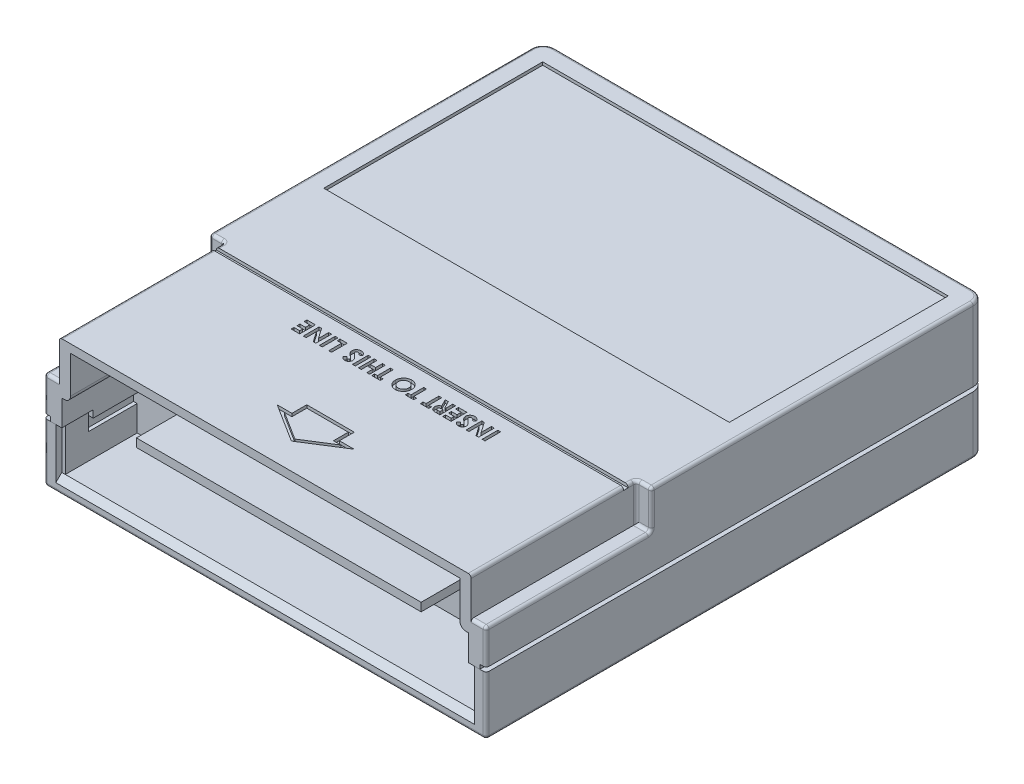
SolidWorks part; units mm, degrees
other "PCB"
other "Back"
other "Front"
ref_plane "Front Plane" through (0, 0, 0) normal (0, 0, 1) x (1, 0, 0)
ref_plane "Top Plane" through (0, 0, 0) normal (0, 1, 0) x (1, 0, 0)
ref_plane "Right Plane" through (0, 0, 0) normal (1, 0, 0) x (0, 0, -1)
sketch "Sketch1" plane through (0, 0, 0) normal (0, 1, 0) x (1, 0, 0)
  line L0 (0, 0) -> (0, 65.8) construction
  line L1 (-23.975, 0) -> (-23.975, 21.47)
  line L2 (-23.975, 21.47) -> (-26.93, 21.47)
  line L3 (-26.93, 21.47) -> (-26.93, 65.8)
  line L4 (-26.93, 65.8) -> (26.93, 65.8)
  line L5 (26.93, 65.8) -> (26.93, 21.47)
  line L6 (26.93, 21.47) -> (23.975, 21.47)
  line L7 (23.975, 21.47) -> (23.975, 0)
  line L8 (23.975, 0) -> (-23.975, 0)
  line L9 (-20.025, 17.13) -> (20.025, 17.13) construction
  circle A0 centre (-20.025, 19.03) radius 1.9
  circle A1 centre (0, 19.03) radius 2.65
  circle A2 centre (20.025, 19.03) radius 1.9
  point P16 (0, 0)
  dimension "D5" = 3.8
  dimension "D8" = 5.3
  dimension "D1" = 53.86
  dimension "D2" = 44.33
  dimension "D3" = 65.8
  dimension "D4" = 47.95
  dimension "D6" = 36.25
  dimension "D7" = 17.13
extrude "Boss-Extrude1" add sketch "Sketch1" along normal mid plane 1.6
sketch "Sketch2" plane through (0, 0.8, 0) normal (0, 1, 0) x (1, 0, 0)
  line L0 (0, 0) -> (0, 65.8) construction
  line L1 (-26.125, 39.52) -> (26.125, 39.52)
  line L2 (-26.125, 39.52) -> (-26.125, 25.82)
  line L3 (-26.125, 25.82) -> (26.125, 25.82)
  line L4 (26.125, 39.52) -> (26.125, 25.82)
  line L5 (26.93, 65.8) -> (-26.93, 65.8) construction
  line L6 (-23.975, 0) -> (23.975, 0) construction
  dimension "D1" = 52.25
  dimension "D2" = 13.7
  dimension "D3" = 25.82
extrude "Boss-Extrude2" add sketch "Sketch2" along normal blind 4.4
sketch "Sketch3" plane through (0, 0.8, 0) normal (0, 1, 0) x (1, 0, 0)
  line L0 (26.93, 21.47) -> (26.93, 65.8) construction
  line L1 (11.66, 63.46) -> (22.66, 63.46)
  line L2 (11.66, 63.46) -> (11.66, 42.86)
  line L3 (11.66, 42.86) -> (22.66, 42.86)
  line L4 (22.66, 63.46) -> (22.66, 42.86)
  line L5 (26.93, 65.8) -> (-26.93, 65.8) construction
  dimension "D1" = 20.6
  dimension "D2" = 11
  dimension "D3" = 4.27
  dimension "D4" = 2.34
extrude "Boss-Extrude3" add sketch "Sketch3" along normal blind 2.88
sketch "Sketch4" plane through (0, 0.8, 0) normal (0, 1, 0) x (1, 0, 0)
  line L0 (26.93, 65.8) -> (-26.93, 65.8) construction
  line L1 (0, 54.1) -> (0, 19.03) construction
  circle A0 centre (0, 54.1) radius 1.6
  dimension "D1" = 3.2
  dimension "D2" = 10.1
extrude "Boss-Extrude4" add sketch "Sketch4" along normal blind 6.75
sketch "Sketch5" plane through (0, 0.8, 0) normal (0, 1, 0) x (1, 0, 0)
  line L0 (23.975, 0) -> (23.975, 21.47) construction
  line L1 (-23.975, 0) -> (23.975, 0)
  line L2 (-23.975, 0) -> (-23.975, 8.52)
  line L3 (-23.975, 8.52) -> (23.975, 8.52)
  line L4 (23.975, 0) -> (23.975, 8.52)
  dimension "D1" = 8.52
extrude "Cut-Extrude1" cut sketch "Sketch5" against normal blind 0.1
mirror "Mirror1" about plane through (0, 0, 0) normal (0, 1, 0) of "Cut-Extrude1"
ref_plane "Plane1" through (0, -4.72, 0) normal (0, -1, 0) x (-1, 0, 0)
sketch "Sketch6" plane through (0, -4.72, 0) normal (0, -1, 0) x (-1, 0, 0)
  line L0 (0, 19.03) -> (0, 38.8) construction
  line L1 (-11.845, 38.8) -> (11.845, 38.8)
  line L2 (-11.845, 38.8) -> (-11.845, 80.73)
  line L3 (-11.845, 80.73) -> (11.845, 80.73)
  line L4 (11.845, 38.8) -> (11.845, 80.73)
  line L5 (23.975, 0) -> (-23.975, 0) construction
  dimension "D1" = 41.93
  dimension "D2" = 23.69
  dimension "D3" = 38.8
extrude "Boss-Extrude5" add sketch "Sketch6" along normal blind 1.09 separate body
sketch "Sketch7" plane through (0, -4.72, 0) normal (0, 1, 0) x (1, 0, 0)
  line L0 (0, 80.73) -> (0, 47.8) construction
  line L1 (-7.5, 47.8) -> (7.5, 47.8)
  line L2 (-7.5, 47.8) -> (-7.5, 43.8)
  line L3 (-7.5, 43.8) -> (7.5, 43.8)
  line L4 (7.5, 47.8) -> (7.5, 43.8)
  line L5 (-11.845, 80.73) -> (11.845, 80.73) construction
  line L6 (11.845, 38.8) -> (-11.845, 38.8) construction
  dimension "D1" = 15
  dimension "D2" = 4
  dimension "D3" = 5
extrude "Boss-Extrude6" add sketch "Sketch7" along normal up to next
sketch "Sketch8" plane through (0, -4.72, 0) normal (0, 1, 0) x (1, 0, 0)
  line L0 (-5, 80.73) -> (-3.795, 79.37)
  line L1 (-11.845, 80.73) -> (11.845, 80.73) construction
  line L2 (-3.795, 79.37) -> (3.795, 79.37)
  line L3 (3.795, 79.37) -> (5, 80.73)
  line L4 (5, 80.73) -> (-5, 80.73)
  line L5 (0, 79.37) -> (0, 65.8) construction
  line L6 (26.93, 65.8) -> (-26.93, 65.8) construction
  dimension "D1" = 7.59
  dimension "D2" = 1.36
  dimension "D3" = 10
extrude "Cut-Extrude2" cut sketch "Sketch8" against normal through all both and the other way through all
sketch "Sketch9" plane through (0, -4.72, 0) normal (0, 1, 0) x (1, 0, 0)
  line L0 (0, 79.37) -> (0, 77.88) construction
  line L1 (-7.5, 77.88) -> (7.5, 77.88)
  line L2 (-7.5, 77.88) -> (-7.5, 62.13)
  line L3 (-7.5, 62.13) -> (7.5, 62.13)
  line L4 (7.5, 77.88) -> (7.5, 62.13)
  line L5 (-3.795, 79.37) -> (3.795, 79.37) construction
  line L6 (-11.845, 80.73) -> (-5, 80.73) construction
  dimension "D1" = 15
  dimension "D2" = 2.85
  dimension "D3" = 15.75
extrude "Boss-Extrude7" add sketch "Sketch9" along normal blind 1.95
sketch "Sketch41" plane through (0, 0, -77.88) normal (0, 0, -1) x (-1, 0, 0)
  line L1 (-6.63, -2.87) -> (4.39, -2.87)
  line L2 (-6.63, -2.87) -> (-6.63, -3.87)
  line L3 (-6.63, -3.87) -> (4.39, -3.87)
  line L4 (4.39, -2.87) -> (4.39, -3.87)
  line L5 (-7.5, -2.77) -> (-7.5, -4.72) construction
  line L6 (-7.5, -2.77) -> (7.5, -2.77) construction
  dimension "D1" = 11.02
  dimension "D2" = 0.87
  dimension "D3" = 0.1
  dimension "D4" = 1
extrude "Boss-Extrude25" add sketch "Sketch41" along normal blind 2.42 separate body
sketch "Sketch10" plane through (0, 0.8, 0) normal (0, 1, 0) x (1, 0, 0)
  line L0 (0, 0) -> (0, 87.284) construction
  circle A0 centre (-20.025, 19.03) radius 1.73
  circle A1 centre (0, 19.03) radius 2.47
  circle A2 centre (20.025, 19.03) radius 1.73
  circle A3 centre (0, 19.03) radius 1.515
  circle A4 centre (-27, 73.03) radius 3.28
  circle A5 centre (27, 73.03) radius 3.28
  circle A6 centre (-27, 73.03) radius 1.515
  circle A7 centre (27, 73.03) radius 1.515
  dimension "D1" = 3.46
  dimension "D2" = 4.94
  dimension "D3" = 3.03
  dimension "D4" = 6.56
  dimension "D5" = 54
  dimension "D6" = 54
extrude "Boss-Extrude8" add sketch "Sketch10" against normal up to surface (1.6 mm away) separate body up to face at (0, -0.8, -16.38)
sketch "Sketch11" plane through (0, -0.8, 0) normal (0, -1, 0) x (1, 0, 0)
  circle A0 centre (20.025, -19.03) radius 2.5
  circle A1 centre (-20.025, -19.03) radius 2.5
  circle A2 centre (0, -19.03) radius 1.515
  circle A3 centre (0, -19.03) radius 3.28
  circle A4 centre (0, -19.03) radius 1.515 construction
  circle A5 centre (27, -73.03) radius 3.28 construction
  circle A6 centre (-27, -73.03) radius 3.28 construction
  circle A7 centre (27, -73.03) radius 3.28
  circle A8 centre (-27, -73.03) radius 3.28
  circle A9 centre (-27, -73.03) radius 1.515 construction
  circle A10 centre (27, -73.03) radius 1.515 construction
  circle A11 centre (-27, -73.03) radius 1.515
  circle A12 centre (27, -73.03) radius 1.515
  dimension "D1" = 5
  dimension "D2" = 6.56
extrude "Boss-Extrude9" add sketch "Sketch11" along normal blind 8.535 separate body
sketch "Sketch12" plane through (0, -9.335, 0) normal (0, -1, 0) x (1, 0, 0)
  circle A0 centre (0, -19.03) radius 1.515
  circle A1 centre (0, -19.03) radius 4.625
  circle A2 centre (0, -19.03) radius 1.515 construction
  circle A3 centre (-27, -73.03) radius 4.625
  circle A4 centre (27, -73.03) radius 4.625
  circle A5 centre (-27, -73.03) radius 1.515
  circle A6 centre (27, -73.03) radius 1.515
  dimension "D1" = 9.25
extrude "Boss-Extrude10" add sketch "Sketch12" against normal blind 2.3 separate body
sketch "Sketch13" plane through (0, -9.335, 0) normal (0, -1, 0) x (1, 0, 0)
  line L0 (-37.215, 2.285) -> (37.215, 2.285)
  line L1 (37.215, 2.285) -> (37.215, -81.73)
  line L2 (37.215, -81.73) -> (-37.215, -81.73)
  line L3 (-37.215, -81.73) -> (-37.215, 2.285)
  line L4 (0, 0) -> (0, 2.285) construction
  line L5 (-11.845, -80.73) -> (-5, -80.73) construction
  circle A0 centre (0, -19.03) radius 1.515 construction
  circle A1 centre (0, -19.03) radius 1.515 construction
  circle A2 centre (0, -19.03) radius 1.515
  circle A3 centre (27, -73.03) radius 1.515 construction
  circle A4 centre (-27, -73.03) radius 1.515 construction
  circle A5 centre (27, -73.03) radius 1.515
  circle A6 centre (-27, -73.03) radius 1.515
  dimension "D3" = 19.8
  dimension "D1" = 74.43
  dimension "D2" = 1
extrude "Boss-Extrude11" add sketch "Sketch13" along normal blind 2.35 separate body
fillet "Fillet1" radius 2 2 edges at (37.215, -10.51, -81.73) (-37.215, -10.51, -81.73)
sketch "Sketch14" plane through (0, -9.335, 0) normal (0, 1, 0) x (1, 0, 0)
  line L0 (-35.265, -2.285) -> (-35.265, 77.43)
  line L1 (-33.265, 79.43) -> (33.265, 79.43)
  line L2 (35.265, 77.43) -> (35.265, -2.285)
  line L3 (35.265, -2.285) -> (37.215, -2.285)
  line L4 (37.215, -2.285) -> (37.215, 79.73)
  line L5 (35.215, 81.73) -> (-35.215, 81.73)
  line L6 (-37.215, 79.73) -> (-37.215, -2.285)
  line L7 (-37.215, -2.285) -> (37.215, -2.285)
  line L8 (37.215, -2.285) -> (37.215, 79.73)
  line L9 (35.215, 81.73) -> (-35.215, 81.73)
  line L10 (-37.215, 79.73) -> (-37.215, -2.285)
  line L11 (-37.215, -2.285) -> (-35.265, -2.285)
  arc A0 (33.265, 79.43) -> (35.265, 77.43) centre (33.265, 77.43) cw
  arc A1 (-35.265, 77.43) -> (-33.265, 79.43) centre (-33.265, 77.43) cw
  arc A2 (37.215, 79.73) -> (35.215, 81.73) centre (35.215, 79.73) ccw
  arc A3 (-35.215, 81.73) -> (-37.215, 79.73) centre (-35.215, 79.73) ccw
  arc A4 (37.215, 79.73) -> (35.215, 81.73) centre (35.215, 79.73) ccw
  arc A5 (-35.215, 81.73) -> (-37.215, 79.73) centre (-35.215, 79.73) ccw
  dimension "D5" = 2
  dimension "D2" = 1.95
  dimension "D3" = 2.3
  dimension "D4" = 1.95
  dimension "D1" = 0
extrude "Boss-Extrude12" add sketch "Sketch14" along normal blind 7.49 separate body
combine bodies "Combine1" operation type add bodies to combine 111 119 118 117 116 115 114 113 112 119 118 117 116 115 114 113 112 152 151 148 153 150 149
sketch "Sketch21" plane through (0, 0, -79.43) normal (0, 0, 1) x (1, 0, 0)
  line L0 (11.845, -5.81) -> (-11.845, -5.81) construction
  line L1 (-12.345, -2.64) -> (12.345, -2.64)
  line L2 (-12.345, -2.64) -> (-12.345, -6.06)
  line L3 (-12.345, -6.06) -> (12.345, -6.06)
  line L4 (12.345, -2.64) -> (12.345, -6.06)
  line L5 (-11.845, -5.81) -> (-11.845, -4.72) construction
  line L6 (11.845, -5.81) -> (11.845, -4.72) construction
  line L7 (-7.5, -2.77) -> (7.5, -2.77) construction
  dimension "D1" = 0.25
  dimension "D2" = 0.5
  dimension "D3" = 0.5
  dimension "D4" = 0.13
extrude "Cut-Extrude4" cut sketch "Sketch21" against normal blind 1.4 and the other way blind 10
chamfer "Chamfer1" distance 1 angle 45 1 edges at (0, -9.335, 2.285)
ref_plane "Plane2" through (0, 0, -10.815) normal (0, 0, 1) x (1, 0, 0)
sketch "Sketch15" plane through (0, -9.335, 0) normal (0, 1, 0) x (1, 0, 0)
  line L0 (35.265, 77.43) -> (35.265, -2.285) construction
  line L1 (-33.265, 79.43) -> (33.265, 79.43) construction
  line L2 (-35.265, -1.285) -> (-35.265, 77.43) construction
  line L3 (35.265, 77.43) -> (35.265, -1.285)
  line L4 (-33.265, 79.43) -> (33.265, 79.43)
  line L5 (-35.265, -1.285) -> (-35.265, 77.43)
  line L6 (-34.665, -1.285) -> (-34.665, 77.43)
  line L7 (-33.265, 78.83) -> (33.265, 78.83)
  line L8 (34.665, 77.43) -> (34.665, -1.285)
  line L11 (-35.265, -1.285) -> (-34.665, -1.285)
  line L12 (34.665, -1.285) -> (35.265, -1.285)
  line L13 (35.265, -2.285) -> (-35.265, -2.285) construction
  line L14 (35.265, 77.43) -> (35.265, -2.285) construction
  line L15 (34.665, 77.43) -> (34.665, -2.285) construction
  line L17 (-35.265, -1.285) -> (-35.265, 77.43) construction
  line L18 (-34.665, -1.285) -> (-34.665, 77.43) construction
  arc A0 (35.265, 77.43) -> (33.265, 79.43) centre (33.265, 77.43) ccw construction
  arc A1 (-33.265, 79.43) -> (-35.265, 77.43) centre (-33.265, 77.43) ccw construction
  arc A2 (35.265, 77.43) -> (33.265, 79.43) centre (33.265, 77.43) ccw
  arc A3 (-33.265, 79.43) -> (-35.265, 77.43) centre (-33.265, 77.43) ccw
  arc A4 (-33.265, 78.83) -> (-34.665, 77.43) centre (-33.265, 77.43) ccw
  arc A5 (34.665, 77.43) -> (33.265, 78.83) centre (33.265, 77.43) ccw
  dimension "D2" = 1
  dimension "D1" = 0.6
extrude "Boss-Extrude13" add sketch "Sketch15" along normal blind 4.3
sketch "Sketch17" plane through (0, -5.035, 0) normal (0, 1, 0) x (1, 0, 0)
  line L0 (-35.265, -2.285) -> (-35.265, 77.43) construction
  line L1 (-34.665, -1.285) -> (-35.265, -1.285)
  line L2 (-34.665, -1.285) -> (-34.665, 2.615)
  line L3 (-34.665, 2.615) -> (-35.265, 2.615)
  line L4 (-35.265, -1.285) -> (-35.265, 2.615)
  dimension "D1" = 3.9
extrude "Boss-Extrude14" add sketch "Sketch17" along normal up to surface (3.19 mm away) up to face at (0, -1.845, -52.4297)
mirror "Mirror2" about plane through (0, 0, 0) normal (1, 0, 0) of "Boss-Extrude14"
sketch "Sketch18" plane through (0, 0, -10.815) normal (0, 0, 1) x (1, 0, 0)
  line L0 (-34.665, -9.335) -> (-34.665, -5.035)
  line L1 (-34.665, -5.035) -> (-35.265, -5.035)
  line L2 (-35.265, -5.035) -> (-35.265, -3.095)
  line L3 (-35.265, -1.845) -> (-35.265, -10.335) construction
  line L4 (-35.265, -3.095) -> (-33.965, -3.095)
  line L5 (-33.965, -3.095) -> (-33.965, 1.21)
  line L6 (-33.965, 1.21) -> (-24.215, 1.21)
  line L7 (-24.215, 1.21) -> (-24.215, -1.09)
  line L8 (-24.215, -1.09) -> (24.215, -1.09)
  line L9 (24.215, -1.09) -> (24.215, 1.21)
  line L10 (24.215, 1.21) -> (33.965, 1.21)
  line L11 (33.965, 1.21) -> (33.965, -3.095)
  line L12 (33.965, -3.095) -> (35.265, -3.095)
  line L13 (35.265, -3.095) -> (35.265, -5.035)
  line L14 (35.265, -5.035) -> (34.665, -5.035)
  line L15 (34.665, -5.035) -> (34.665, -9.335)
  line L16 (34.665, -9.335) -> (-34.665, -9.335)
  line L17 (-37.215, -1.845) -> (-35.265, -1.845) construction
  line L18 (0, -9.335) -> (0, -1.09) construction
  line L19 (-37.215, -1.845) -> (-37.215, -11.685) construction
  dimension "D1" = 1.25
  dimension "D2" = 9.75
  dimension "D3" = 3.25
  dimension "D4" = 10.545
  dimension "D5" = 8.245
extrude "Boss-Extrude15" add sketch "Sketch18" against normal blind 1.7
sketch "Sketch19" plane through (0, -9.335, 0) normal (0, 1, 0) x (1, 0, 0)
  line L0 (0, 0) -> (0, 7.9552) construction
  line L1 (-34.665, 12.515) -> (34.665, 12.515) construction
  circle A0 centre (-20, 57.515) radius 3
  circle A1 centre (20, 57.515) radius 3
  dimension "D2" = 6
  dimension "D3" = 45
  dimension "D1" = 40
extrude "Boss-Extrude16" add sketch "Sketch19" along normal up to next
sketch "Sketch20" plane through (0, -11.685, 0) normal (0, -1, 0) x (1, 0, 0)
  circle A0 centre (0, -19.03) radius 2.95
  circle A1 centre (-27, -73.03) radius 2.95
  circle A2 centre (27, -73.03) radius 2.95
  dimension "D1" = 5.9
extrude "Cut-Extrude3" cut sketch "Sketch20" against normal blind 2.45
sketch "Sketch23" plane through (0, 0, -81.73) normal (0, 0, -1) x (-1, 0, 0)
  line L1 (-7.13, -4.37) -> (4.89, -4.37)
  line L2 (-7.13, -4.37) -> (-7.13, -2.64)
  line L3 (-7.13, -2.64) -> (4.89, -2.64)
  line L4 (4.89, -4.37) -> (4.89, -2.64)
  line L8 (-6.63, -2.87) -> (-6.63, -3.87) construction
  line L9 (4.39, -3.87) -> (4.39, -2.87) construction
  line L10 (-6.63, -3.87) -> (4.39, -3.87) construction
  line L11 (4.39, -2.87) -> (-6.63, -2.87) construction
  dimension "D1" = 0.5
  dimension "D2" = 0.5
  dimension "D3" = 0.5
  dimension "D4" = 0.23
extrude "Cut-Extrude5" cut sketch "Sketch23" along normal through all and the other way blind 30.88
fillet "Fillet2" radius 0.5 8 edges at (-37.215, -11.685, -38.7225) (-36.6292, -11.685, -81.1442) (0, -11.685, -81.73) (36.6292, -11.685, -81.1442) (37.215, -11.685, -38.7225) (0, -11.685, 2.285) (37.215, -6.765, 2.285) (-37.215, -6.765, 2.285)
sketch "Sketch39" plane through (0, 0, -78.83) normal (0, 0, 1) x (1, 0, 0)
  line L1 (-12.345, -5.035) -> (12.345, -5.035)
  line L2 (-12.345, -5.035) -> (-12.345, -6.06)
  line L3 (-12.345, -6.06) -> (12.345, -6.06)
  line L4 (12.345, -5.035) -> (12.345, -6.06)
extrude "Cut-Extrude11" cut sketch "Sketch39" against normal up to surface (0.6 mm away) up to face at (0, -5.5475, -79.43)
sketch "Sketch24" plane through (0, -1.845, 0) normal (0, 1, 0) x (1, 0, 0)
  line L0 (35.265, 77.43) -> (35.265, 2.615) construction
  line L1 (-33.265, 79.43) -> (33.265, 79.43) construction
  line L2 (-35.265, 2.615) -> (-35.265, 77.43) construction
  line L3 (35.265, 77.43) -> (35.265, 2.615)
  line L4 (-33.265, 79.43) -> (33.265, 79.43)
  line L5 (-35.265, 2.615) -> (-35.265, 77.43)
  line L6 (-36.145, 2.615) -> (-36.145, 77.43)
  line L7 (-33.265, 80.31) -> (33.265, 80.31)
  line L8 (36.145, 77.43) -> (36.145, 2.615)
  line L9 (-35.265, 2.615) -> (-35.265, -2.285)
  line L10 (-35.265, -2.285) -> (-36.145, -2.285)
  line L11 (-36.145, -2.285) -> (-36.145, 2.615)
  line L12 (35.265, 2.615) -> (35.265, -2.285)
  line L13 (35.265, -2.285) -> (36.145, -2.285)
  line L14 (36.145, -2.285) -> (36.145, 2.615)
  arc A0 (35.265, 77.43) -> (33.265, 79.43) centre (33.265, 77.43) ccw construction
  arc A1 (-33.265, 79.43) -> (-35.265, 77.43) centre (-33.265, 77.43) ccw construction
  arc A2 (35.265, 77.43) -> (33.265, 79.43) centre (33.265, 77.43) ccw
  arc A3 (-33.265, 79.43) -> (-35.265, 77.43) centre (-33.265, 77.43) ccw
  arc A4 (-33.265, 80.31) -> (-36.145, 77.43) centre (-33.265, 77.43) ccw
  arc A5 (36.145, 77.43) -> (33.265, 80.31) centre (33.265, 77.43) ccw
  dimension "D1" = 0.88
extrude "Boss-Extrude17" add sketch "Sketch24" along normal blind 0.72 separate body
sketch "Sketch25" plane through (0, -1.125, 0) normal (0, 1, 0) x (1, 0, 0)
  line L1 (-37.215, 79.73) -> (-37.215, -1.785) construction
  line L2 (35.215, 81.73) -> (-35.215, 81.73) construction
  line L3 (37.215, -1.785) -> (37.215, 79.73) construction
  line L5 (35.265, 77.43) -> (35.265, -2.285) construction
  line L6 (-33.265, 79.43) -> (33.265, 79.43) construction
  line L7 (-35.265, -2.285) -> (-35.265, 77.43) construction
  line L9 (-37.215, 79.73) -> (-37.215, -1.785)
  line L10 (35.215, 81.73) -> (-35.215, 81.73)
  line L11 (37.215, -1.785) -> (37.215, 79.73)
  line L13 (35.265, 77.43) -> (35.265, -2.285)
  line L14 (-33.265, 79.43) -> (33.265, 79.43)
  line L15 (-35.265, -2.285) -> (-35.265, 77.43)
  line L16 (-36.715, -2.285) -> (-35.265, -2.285) construction
  line L17 (-36.715, -2.285) -> (-35.265, -2.285)
  line L18 (35.265, -2.285) -> (36.715, -2.285) construction
  line L19 (35.265, -2.285) -> (36.715, -2.285)
  arc A0 (-35.215, 81.73) -> (-37.215, 79.73) centre (-35.215, 79.73) ccw construction
  arc A1 (37.215, 79.73) -> (35.215, 81.73) centre (35.215, 79.73) ccw construction
  arc A2 (35.265, 77.43) -> (33.265, 79.43) centre (33.265, 77.43) ccw construction
  arc A3 (-33.265, 79.43) -> (-35.265, 77.43) centre (-33.265, 77.43) ccw construction
  arc A4 (-35.215, 81.73) -> (-37.215, 79.73) centre (-35.215, 79.73) ccw
  arc A5 (37.215, 79.73) -> (35.215, 81.73) centre (35.215, 79.73) ccw
  arc A6 (35.265, 77.43) -> (33.265, 79.43) centre (33.265, 77.43) ccw
  arc A7 (-33.265, 79.43) -> (-35.265, 77.43) centre (-33.265, 77.43) ccw
  arc A8 (-37.215, -1.785) -> (-36.715, -2.285) centre (-36.715, -1.785) ccw construction
  arc A9 (-37.215, -1.785) -> (-36.715, -2.285) centre (-36.715, -1.785) ccw
  arc A10 (36.715, -2.285) -> (37.215, -1.785) centre (36.715, -1.785) ccw construction
  arc A11 (36.715, -2.285) -> (37.215, -1.785) centre (36.715, -1.785) ccw
extrude "Boss-Extrude18" add sketch "Sketch25" along normal blind 12.29 separate body
sketch "Sketch26" plane through (0, 11.165, 0) normal (0, 1, 0) x (1, 0, 0)
  line L0 (35.265, 77.43) -> (35.265, -2.285) construction
  line L1 (-33.265, 79.43) -> (33.265, 79.43) construction
  line L2 (-35.265, -2.285) -> (-35.265, 77.43) construction
  line L3 (35.265, 77.43) -> (35.265, -2.285)
  line L4 (-33.265, 79.43) -> (33.265, 79.43)
  line L5 (-35.265, -2.285) -> (-35.265, 77.43)
  line L6 (-35.265, -2.285) -> (35.265, -2.285)
  arc A0 (35.265, 77.43) -> (33.265, 79.43) centre (33.265, 77.43) ccw construction
  arc A1 (-33.265, 79.43) -> (-35.265, 77.43) centre (-33.265, 77.43) ccw construction
  arc A2 (35.265, 77.43) -> (33.265, 79.43) centre (33.265, 77.43) ccw
  arc A3 (-33.265, 79.43) -> (-35.265, 77.43) centre (-33.265, 77.43) ccw
extrude "Boss-Extrude19" add sketch "Sketch26" against normal blind 2.39 separate body
sketch "Sketch28" plane through (0, 0, 2.285) normal (0, 0, 1) x (1, 0, 0)
  line L1 (-35.265, 8.775) -> (-32.795, 8.775)
  line L2 (-35.265, 8.775) -> (-35.265, 2.515)
  line L3 (-35.265, 2.515) -> (-32.795, 2.515)
  line L4 (-32.795, 8.775) -> (-32.795, 2.515)
  line L5 (35.265, 8.775) -> (32.795, 8.775)
  line L6 (35.265, 8.775) -> (35.265, 2.515)
  line L7 (35.265, 2.515) -> (32.795, 2.515)
  line L8 (32.795, 8.775) -> (32.795, 2.515)
  dimension "D1" = 2.47
  dimension "D2" = 6.26
extrude "Boss-Extrude20" add sketch "Sketch28" against normal blind 30.88 separate body
combine bodies "Combine2" operation type add bodies to combine 134 131 133 130 129
sketch "Sketch29" plane through (0, 11.165, 0) normal (0, 1, 0) x (1, 0, 0)
  line L0 (-37.215, 79.73) -> (-37.215, -1.785) construction
  line L1 (-37.215, 25.525) -> (-34.685, 25.525)
  line L2 (-37.215, 25.525) -> (-37.215, -2.285)
  line L3 (-37.215, -2.285) -> (-34.685, -2.285)
  line L4 (-34.685, 25.525) -> (-34.685, -2.285)
  line L5 (-36.715, -2.285) -> (36.715, -2.285) construction
  line L6 (37.215, -1.785) -> (37.215, 79.73) construction
  line L7 (37.215, 25.525) -> (34.685, 25.525)
  line L8 (37.215, 25.525) -> (37.215, -2.285)
  line L9 (37.215, -2.285) -> (34.685, -2.285)
  line L10 (34.685, 25.525) -> (34.685, -2.285)
  line L11 (0, 0) -> (0, 27.6033) construction
  dimension "D1" = 2.53
  dimension "D2" = 27.81
extrude "Cut-Extrude6" cut sketch "Sketch29" against normal blind 6.42
sketch "Sketch30" plane through (0, 0, -10.815) normal (0, 0, 1) x (1, 0, 0)
  line L0 (-32.795, 8.775) -> (32.795, 8.775)
  line L1 (32.795, 8.775) -> (32.795, 2.515)
  line L2 (32.795, 2.515) -> (35.265, 2.515)
  line L3 (35.265, 2.515) -> (35.265, 1.21)
  line L4 (35.265, 2.515) -> (35.265, -1.845) construction
  line L5 (35.265, 1.21) -> (-35.265, 1.21)
  line L6 (-35.265, 8.775) -> (-35.265, -1.845) construction
  line L7 (-35.265, 1.21) -> (-35.265, 2.515)
  line L8 (-35.265, 2.515) -> (-32.795, 2.515)
  line L9 (-32.795, 2.515) -> (-32.795, 8.775)
  line L10 (-24.215, 1.21) -> (-33.965, 1.21) construction
extrude "Boss-Extrude21" add sketch "Sketch30" against normal up to surface (1.7 mm away) up to face at (0, -3.0331, -12.515)
ref_plane "Plane3" through (0, -3.075, 0) normal (0, -1, 0) x (-1, 0, 0)
sketch "Sketch31" plane through (0, -3.075, 0) normal (0, -1, 0) x (-1, 0, 0)
  line L0 (35.265, -2.285) -> (35.265, 77.43) construction
  line L1 (-33.265, 79.43) -> (33.265, 79.43) construction
  line L2 (-35.265, 77.43) -> (-35.265, -2.285) construction
  line L3 (35.265, -2.285) -> (35.265, 77.43)
  line L4 (-33.265, 79.43) -> (33.265, 79.43)
  line L5 (-35.265, 77.43) -> (-35.265, -2.285)
  line L6 (34.265, -2.285) -> (34.265, 77.43)
  line L7 (-33.265, 78.43) -> (33.265, 78.43)
  line L8 (-34.265, 77.43) -> (-34.265, -2.285)
  line L9 (-35.265, -2.285) -> (-34.265, -2.285)
  line L10 (34.265, -2.285) -> (35.265, -2.285)
  arc A0 (35.265, 77.43) -> (33.265, 79.43) centre (33.265, 77.43) ccw construction
  arc A1 (-33.265, 79.43) -> (-35.265, 77.43) centre (-33.265, 77.43) ccw construction
  arc A2 (35.265, 77.43) -> (33.265, 79.43) centre (33.265, 77.43) ccw
  arc A3 (-33.265, 79.43) -> (-35.265, 77.43) centre (-33.265, 77.43) ccw
  arc A4 (34.265, 77.43) -> (33.265, 78.43) centre (33.265, 77.43) ccw
  arc A5 (-33.265, 78.43) -> (-34.265, 77.43) centre (-33.265, 77.43) ccw
  dimension "D1" = 1
extrude "Boss-Extrude22" add sketch "Sketch31" against normal up to next
sketch "Sketch32" plane through (0, -3.075, 0) normal (0, -1, 0) x (1, 0, 0)
  line L0 (-35.265, 2.285) -> (-35.265, -77.43) construction
  line L1 (-34.265, -10.815) -> (-35.265, -10.815)
  line L2 (-34.265, -10.815) -> (-34.265, -16.815)
  line L3 (-34.265, -16.815) -> (-35.265, -16.815)
  line L4 (-35.265, -10.815) -> (-35.265, -16.815)
  line L5 (0, 0) -> (0, -20.9928) construction
  line L6 (35.265, -10.815) -> (35.265, -16.815)
  line L7 (34.265, -16.815) -> (35.265, -16.815)
  line L8 (34.265, -10.815) -> (34.265, -16.815)
  line L9 (34.265, -10.815) -> (35.265, -10.815)
  dimension "D1" = 6
extrude "Cut-Extrude7" cut sketch "Sketch32" against normal up to surface (4.285 mm away) up to face at (0, 1.21, -11.665)
sketch "Sketch33" plane through (0, 1.21, 0) normal (0, -1, 0) x (1, 0, 0)
  line L1 (-34.265, -12.515) -> (-35.265, -12.515)
  line L2 (-34.265, -12.515) -> (-34.265, -16.815)
  line L3 (-34.265, -16.815) -> (-35.265, -16.815)
  line L4 (-35.265, -12.515) -> (-35.265, -16.815)
  line L5 (34.265, -12.515) -> (35.265, -12.515)
  line L6 (34.265, -12.515) -> (34.265, -16.815)
  line L7 (34.265, -16.815) -> (35.265, -16.815)
  line L8 (35.265, -12.515) -> (35.265, -16.815)
extrude "Cut-Extrude8" cut sketch "Sketch33" against normal up to surface (1.305 mm away) up to face at (-33.53, 2.515, -20.555)
sketch "Sketch34" plane through (0, -3.075, 0) normal (0, -1, 0) x (1, 0, 0)
  line L0 (-34.265, -10.815) -> (-34.265, 2.285) construction
  line L1 (-35.265, 2.285) -> (-34.265, 2.285)
  line L2 (-35.265, 2.285) -> (-35.265, -3.015)
  line L3 (-35.265, -3.015) -> (-34.265, -3.015)
  line L4 (-34.265, 2.285) -> (-34.265, -3.015)
  line L5 (34.265, 2.285) -> (34.265, -10.815) construction
  line L6 (35.265, 2.285) -> (34.265, 2.285)
  line L7 (35.265, 2.285) -> (35.265, -3.015)
  line L8 (35.265, -3.015) -> (34.265, -3.015)
  line L9 (34.265, 2.285) -> (34.265, -3.015)
  dimension "D1" = 5.3
extrude "Cut-Extrude9" cut sketch "Sketch34" against normal up to surface (1.23 mm away) up to face at (0, -1.845, -42.3338)
fillet "Fillet3" radius 1 6 edges at (32.795, 5.645, -28.595) (32.795, 2.515, -20.555) (-32.795, 5.645, -28.595) (-32.795, 2.515, -20.555) (-32.795, 2.515, -4.265) (32.795, 2.515, -4.265)
chamfer "Chamfer2" distance 1 angle 45 1 edges at (0, 8.775, 2.285)
sketch "Sketch35" plane through (0, 8.775, 0) normal (0, -1, 0) x (1, 0, 0)
  line L0 (0, 0) -> (0, -3.837) construction
  line L1 (33.265, -78.43) -> (-33.265, -78.43) construction
  circle A0 centre (-26, -65.43) radius 2.5
  circle A1 centre (26, -65.43) radius 2.5
  dimension "D1" = 5
  dimension "D2" = 13
  dimension "D3" = 52
extrude "Boss-Extrude23" add sketch "Sketch35" along normal up to surface (7.975 mm away) up to face at (0, 0.8, -55.7)
sketch "Sketch36" plane through (0, 8.775, 0) normal (0, -1, 0) x (1, 0, 0)
  circle A0 centre (0, -19.03) radius 1.515
  circle A1 centre (0, -19.03) radius 3.28
  circle A2 centre (-27, -73.03) radius 1.515
  circle A3 centre (-27, -73.03) radius 3.28
  circle A4 centre (27, -73.03) radius 1.515
  circle A5 centre (27, -73.03) radius 3.28
  dimension "D1" = 6.56
  dimension "D2" = 3.03
extrude "Boss-Extrude24" add sketch "Sketch36" along normal up to surface (7.975 mm away) up to face at (0, 0.8, -17.515)
sketch "Sketch38" plane through (0, 11.165, 0) normal (0, 1, 0) x (1, 0, 0)
  line L0 (-34.685, -2.285) -> (-34.685, 25.525) construction
  line L1 (-34.685, 24.165) -> (34.685, 24.165)
  line L2 (-34.685, 24.165) -> (-34.685, 23.395)
  line L3 (-34.685, 23.395) -> (34.685, 23.395)
  line L4 (34.685, 24.165) -> (34.685, 23.395)
  line L5 (34.685, 25.525) -> (34.685, -2.285) construction
  line L6 (-3.5, 5.715) -> (-3.5, 8.215)
  line L7 (-3.5, 8.215) -> (3.5, 8.215)
  line L8 (3.5, 8.215) -> (3.5, 5.715)
  line L9 (3.5, 5.715) -> (4.75, 5.715)
  line L10 (4.75, 5.715) -> (0, 2.715)
  line L11 (0, 2.715) -> (-4.75, 5.715)
  line L12 (-4.75, 5.715) -> (-3.5, 5.715)
  line L13 (-34.685, -2.285) -> (34.685, -2.285) construction
  line L14 (0, 0) -> (0, 8.215) construction
  line L15 (-4, 6.215) -> (-4, 8.715)
  line L16 (-4, 8.715) -> (4, 8.715)
  line L17 (4, 8.715) -> (4, 6.215)
  line L18 (4, 6.215) -> (6.478, 6.215)
  line L19 (6.478, 6.215) -> (0, 2.1236)
  line L20 (0, 2.1236) -> (-6.478, 6.215)
  line L21 (-6.478, 6.215) -> (-4, 6.215)
  line L22 (35.215, 81.73) -> (-35.215, 81.73) construction
  line L23 (34.685, 21.095) -> (-34.685, 21.095) construction
  line L24 (-34.15, 78.6) -> (34.15, 78.6)
  line L25 (-34.15, 78.6) -> (-34.15, 41.73)
  line L26 (-34.15, 41.73) -> (34.15, 41.73)
  line L27 (34.15, 78.6) -> (34.15, 41.73)
  line L28 (34.685, 25.525) -> (34.685, -2.285) construction
  text T0 "INSERT TO THIS LINE" font "Century Gothic" height in points 10
  dimension "D1" = 0.77
  dimension "D2" = 25.68
  dimension "D3" = 7
  dimension "D4" = 9.5
  dimension "D5" = 2.5
  dimension "D6" = 5.5
  dimension "D7" = 5
  dimension "D9" = 36.87
  dimension "D10" = 68.3
  dimension "D11" = 3.13
  dimension "D12" = 2.3
  dimension "D8" = 0.5
extrude "Cut-Extrude10" cut sketch "Sketch38" against normal blind 0.5
fillet "Fillet4" radius 0.5 23 edges at (-35.7, 4.745, 2.285) (35.7, 4.745, 2.285) (-37.0686, 4.745, 2.1386) (37.0686, 4.745, 2.1386) (-34.685, 11.165, -24.845) (-37.215, 4.745, -11.87) (34.685, 11.165, -24.845) (37.215, 4.745, -11.87) (-37.215, 11.165, -52.6275) (-36.6292, 11.165, -81.1442) (0, 11.165, -81.73) (36.6292, 11.165, -81.1442) (-34.685, 7.955, -25.525) (-35.95, 11.165, -25.525) (-37.215, 7.955, -25.525) (-35.95, 4.745, -25.525) (35.95, 11.165, -25.525) (34.685, 7.955, -25.525) (35.95, 4.745, -25.525) (37.215, 7.955, -25.525) (37.215, 11.165, -52.6275) (-34.685, 11.165, -10.555) (34.685, 11.165, -10.555)
sketch "Sketch40" plane through (0, 0, -79.43) normal (0, 0, -1) x (-1, 0, 0)
  line L0 (33.265, -3.075) -> (-33.265, -3.075) construction
  line L1 (-8.25, -3.075) -> (8.25, -3.075)
  line L2 (-8.25, -3.075) -> (-8.25, -2.225)
  line L3 (-8.25, -2.225) -> (8.25, -2.225)
  line L4 (8.25, -3.075) -> (8.25, -2.225)
  line L5 (0, 0) -> (0, -2.225) construction
  dimension "D1" = 0.85
  dimension "D2" = 16.5
extrude "Cut-Extrude12" cut sketch "Sketch40" against normal blind 10
